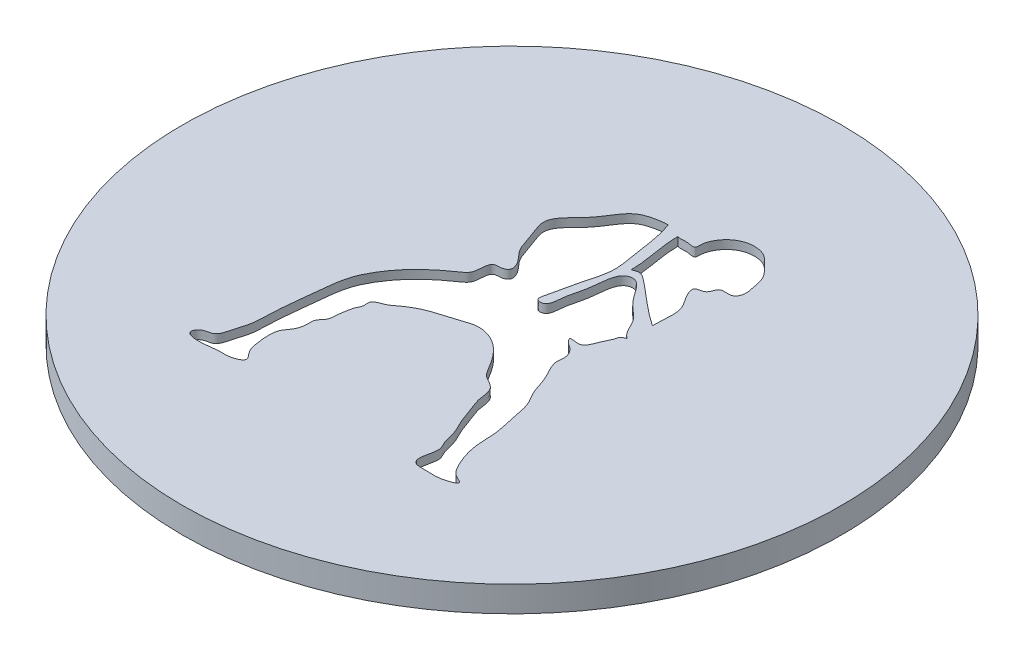
SolidWorks part; units mm, degrees
ref_plane "前视基准面" through (0, 0, 0) normal (0, 0, 1) x (1, 0, 0)
ref_plane "上视基准面" through (0, 0, 0) normal (0, 1, 0) x (1, 0, 0)
ref_plane "右视基准面" through (0, 0, 0) normal (1, 0, 0) x (0, 0, -1)
other "Configuration Table"
sketch "草图1" plane through (0, 0, 0) normal (0, 1, 0) x (1, 0, 0)
  line L0 (72.5003, 135.938) -> (362.5014, 135.938) construction
  circle A0 centre (35, 20) radius 38.5
  spline S0 degree 3 poles (35, 38.2587) (34.6334, 38.2753) (33.6488, 38.1296) (31.3041, 37.5388) (30.1168, 34.3357) (26.7641, 32.007) (28.1551, 29.1291) (28.6711, 26.926) (30.0294, 25.8494) (30.4315, 24.6149) (29.6975, 24.0407) (28.5879, 24.3063) (28.4125, 22.9719) (28.3998, 21.8818) (26.5228, 20.603) (24.5961, 19.0623) (22.8097, 16.6958) (21.5049, 14.2562) (21.2084, 10.6062) (20.7391, 7.2593) (20.7348, 4.8681) (20.5807, 3.5506) (20.1335, 2.3712) (19.7677, 0.4715) (18.3182, 0.588) (17.5197, -0.7471) (19.68, -1.0698) (21.2283, -0.6178) (22.8242, -0.8546) (24.2731, -0.0435) (23.1882, 0.9683) (22.9395, 2.1971) (22.7703, 3.599) (22.8625, 4.9263) (23.768, 5.8744) (24.0071, 6.9767) (23.8804, 8.0801) (24.805, 8.7726) (24.7081, 9.9649) (24.9283, 10.8222) (25.0492, 11.6097) (25.5, 12.1779) (25.1583, 13.2739) (26.5464, 13.5769) (27.6975, 14.5562) (29.6107, 15.6665) (31.8769, 16.1612) (33.7798, 16.9574) (35.5586, 16.7536) (37.2431, 15.7676) (38.3849, 14.3125) (39.0924, 13.0911) (39.6818, 12.219) (40.5359, 11.8842) (41.4881, 11.0869) (41.4522, 9.6174) (42.1486, 8.1152) (42.6393, 6.3745) (43.6145, 4.825) (43.7863, 3.3427) (44.5288, 2.1269) (44.0487, 0.9543) (43.9938, -0.7959) (45.8754, -0.6971) (47.0221, -0.898) (49.5234, -0.092) (47.8088, 0.4695) (47.1412, 1.4615) (46.4736, 2.9504) (45.9845, 4.8862) (46.1, 7.0999) (45.3813, 9.5155) (45.1607, 11.7784) (43.8777, 13.5824) (43.4997, 15.5132) (42.5303, 16.8477) (42.2526, 18.0367) (42.496, 18.9403) (41.8851, 20.1104) (41.0352, 20.4226) (40.5805, 21.2425) (42.1781, 20.664) (42.6572, 21.9009) (43.0113, 22.8056) (43.4042, 23.4716) (43.4739, 24.1735) (43.9373, 24.2795) (44.0946, 24.3748) knots 0.011137 0.011137 0.011137 0.011137 0.017895 0.02884 0.053566 0.076394 0.090782 0.105825 0.117199 0.122579 0.125774 0.132434 0.138902 0.145562 0.152221 0.177469 0.19236 0.206082 0.227671 0.258486 0.268313 0.271611 0.282626 0.293056 0.300381 0.305513 0.314184 0.327372 0.338889 0.344534 0.349971 0.359788 0.368496 0.37585 0.38314 0.391481 0.395963 0.402399 0.409753 0.41628 0.418858 0.424257 0.42873 0.436258 0.443935 0.458083 0.475465 0.48674 0.495169 0.507307 0.52159 0.528495 0.533473 0.540378 0.544929 0.555303 0.564764 0.575464 0.588352 0.597646 0.602528 0.613211 0.62025 0.628803 0.639431 0.649603 0.655454 0.662582 0.672716 0.684786 0.699069 0.712777 0.730949 0.739584 0.752674 0.766304 0.769155 0.774754 0.782934 0.790234 0.791484 0.797641 0.805749 0.812136 0.816139 0.820033 0.823536 0.823536 0.823536 0.823536
  spline S1 degree 3 poles (35, 38.2587) (35.6466, 36.4948) (35.8543, 33.9205) (36.6185, 30.111) (35.504, 27.1203) (35.2499, 24.9915) (34.6219, 22.9169) (36.1408, 22.9697) (36.1037, 25.0782) (36.8129, 26.9102) (36.8461, 28.9964) (37.2866, 30.5026) (39.0892, 31.1743) (40.3546, 28.1901) (42.8794, 26.8281) (43.3402, 24.8219) (44.0946, 24.3748) knots 0 0 0 0 0.166956 0.232571 0.347071 0.429099 0.465182 0.483664 0.532843 0.611757 0.673238 0.722617 0.734592 0.836706 0.924346 1 1 1 1
  spline S2 degree 3 poles (36.7199, 37.6531) (36.7246, 35.4362) (37.3434, 33.9976) (37.3551, 31.5045) (37.8559, 31.7859) (38.4397, 31.7649) (40.7318, 29.9945) (42.336, 28.4282) (44.2684, 27.1376) knots 0 0 0 0 0.408865 0.417465 0.441783 0.484004 0.55011 1 1 1 1
  spline S3 degree 3 poles (44.2684, 27.1376) (44.2534, 27.6534) (44.3416, 28.738) (44.4371, 30.9929) (42.9769, 32.1664) (42.9123, 33.5384) (44.257, 33.3685) (44.2789, 35.1618) (45.9428, 34.4996) (46.5367, 35.681) (46.2733, 36.963) (46.0009, 38.6354) (44.692, 39.7356) (43.7916, 40.7945) (42.47, 41.2245) (41.0652, 41.0524) (39.8526, 40.2616) (39.1045, 39.186) (38.8704, 38.3109) (38.9016, 37.3479) (37.845, 37.7194) (37.1945, 37.5254) (36.8015, 37.6258) (36.7199, 37.6531) knots 0.840262 0.840262 0.840262 0.840262 0.849614 0.86199 0.878687 0.879473 0.885979 0.893394 0.902121 0.907245 0.913938 0.926248 0.936823 0.944332 0.951417 0.961313 0.969271 0.977449 0.984313 0.986958 0.992068 0.998356 1 1 1 1
  dimension "D1" = 77
  dimension "D2" = 35
  dimension "D3" = 20
extrude "凸台-拉伸1" add sketch "草图1" along normal blind 1
sketch "草图2" plane through (0, 0, 0) normal (0, -1, 0) x (-1, 0, 0)
  circle A0 centre (-35, 20) radius 38.5
  circle A1 centre (-35, 20) radius 37.5
  circle A2 centre (-35, 20) radius 38.5 construction
  dimension "D2" = 0
  dimension "D1" = 1
extrude "凸台-拉伸2" add sketch "草图2" along normal blind 2
sketch "草图3" plane through (0, 1, 0) normal (0, 1, 0) x (1, 0, 0)
  circle A0 centre (35, 20) radius 37.5
  circle A1 centre (35, 20) radius 38.5
  circle A2 centre (35, 20) radius 38.5 construction
  dimension "D2" = 0
  dimension "D1" = 1
extrude "凸台-拉伸3" add sketch "草图3" against normal blind 1
